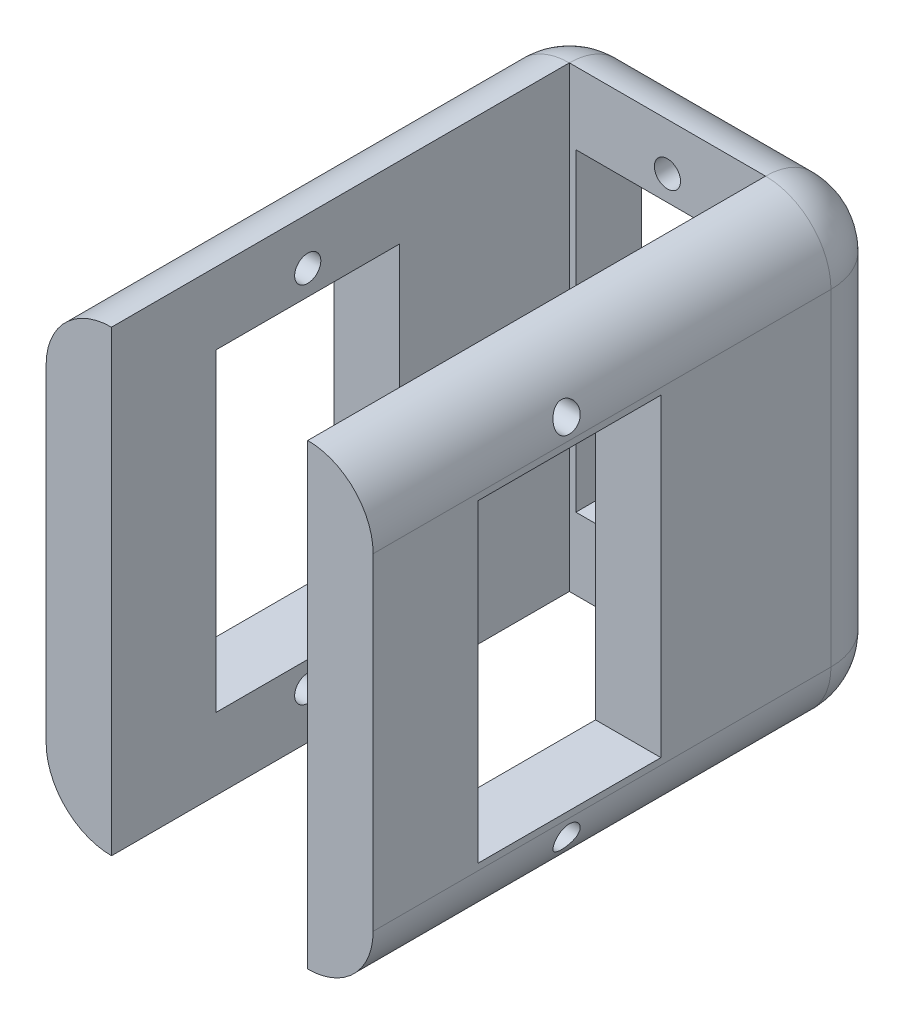
SolidWorks part; units mm, degrees
ref_plane "前视基准面" through (0, 0, 0) normal (0, 0, 1) x (1, 0, 0)
ref_plane "上视基准面" through (0, 0, 0) normal (0, 1, 0) x (1, 0, 0)
ref_plane "右视基准面" through (0, 0, 0) normal (1, 0, 0) x (0, 0, -1)
other "Configuration Table"
sketch "Sketch1" plane through (0, 0, 0) normal (0, 0, 1) x (1, 0, 0)
  line L0 (0, 0) -> (0, 13.9) construction
  line L5 (-10, -17.5) -> (10, -17.5)
  line L6 (-10, -17.5) -> (-10, 17.5)
  line L7 (-10, 17.5) -> (10, 17.5)
  line L8 (10, -17.5) -> (10, 17.5)
  line L9 (-10, -17.5) -> (10, 17.5) construction
  line L10 (-10, 17.5) -> (10, -17.5) construction
  line L11 (-7, -12) -> (7, -12)
  line L12 (-7, -12) -> (-7, 12)
  line L13 (-7, 12) -> (7, 12)
  line L14 (7, -12) -> (7, 12)
  line L15 (-7, -12) -> (7, 12) construction
  line L16 (-7, 12) -> (7, -12) construction
  line L17 (0, 0) -> (10, 0) construction
  circle A0 centre (0, 13.9) radius 1
  circle A1 centre (0, -13.9) radius 1
  point P0 (0, 0)
  point P6 (0, 0)
  dimension "D5" = 2
  dimension "D1" = 20
  dimension "D2" = 35
  dimension "D3" = 14
  dimension "D4" = 24
  dimension "D6" = 13.9
extrude "Boss-Extrude1" add sketch "Sketch1" along normal blind 5
sketch "Sketch2" plane through (-10, 0, 0) normal (-1, 0, 0) x (0, 0, 1)
  line L5 (0, 17.5) -> (40, 17.5)
  line L6 (0, 17.5) -> (0, -17.5)
  line L7 (0, -17.5) -> (40, -17.5)
  line L8 (40, 17.5) -> (40, -17.5)
  dimension "D1" = 35
  dimension "D2" = 40
extrude "Boss-Extrude2" add sketch "Sketch2" along normal mid plane 5 contours L5 L8 L7 L6
sketch "Sketch3" plane through (-7.5, 0, 0) normal (1, 0, 0) x (0, 0, -1)
  line L0 (-5, 0) -> (-25, 0) construction
  line L1 (-5, -17.5) -> (-5, 17.5) construction
  line L2 (-25, 0) -> (-25, 13.9) construction
  line L3 (-35, -17.5) -> (-15, -17.5)
  line L4 (-35, -17.5) -> (-35, 17.5)
  line L5 (-35, 17.5) -> (-15, 17.5)
  line L6 (-15, -17.5) -> (-15, 17.5)
  line L7 (-35, -17.5) -> (-15, 17.5) construction
  line L8 (-35, 17.5) -> (-15, -17.5) construction
  line L9 (-32, -12) -> (-18, -12)
  line L10 (-32, -12) -> (-32, 12)
  line L11 (-32, 12) -> (-18, 12)
  line L12 (-18, -12) -> (-18, 12)
  line L13 (-32, -12) -> (-18, 12) construction
  line L14 (-32, 12) -> (-18, -12) construction
  line L15 (-25, 0) -> (-15, 0) construction
  circle A0 centre (-25, 13.9) radius 1
  circle A1 centre (-25, -13.9) radius 1
  point P6 (-25, 0)
  point P11 (-25, 0)
  dimension "D5" = 2
  dimension "D1" = 20
  dimension "D2" = 35
  dimension "D3" = 14
  dimension "D4" = 24
  dimension "D6" = 13.9
  dimension "D7" = 20
ref_plane "Plane1" through (0, 0, 22.5) normal (0, 0, 1) x (1, 0, 0)
ref_plane "Plane3" through (0, 0, 0) normal (1, 0, 0) x (0, 0, -1)
mirror "Mirror3" about plane through (0, 0, 0) normal (1, 0, 0) of "Boss-Extrude2"
extrude "Cut-Extrude3" cut sketch "Sketch3" against normal through all both and the other way through all contours L9 L12 L11 L10 | A1 | A0 region at (-7.5, 0, 25) region at (-7.5, 13.9, 25) region at (-7.5, -13.9, 25)
fillet "Fillet1" radius 5 8 edges at (0, -17.5, 0) (0, 17.5, 0) (-12.5, 17.5, 20) (-12.5, -17.5, 20) (12.5, 17.5, 20) (12.5, -17.5, 20) (12.5, 0, 0) (-12.5, 0, 0)
